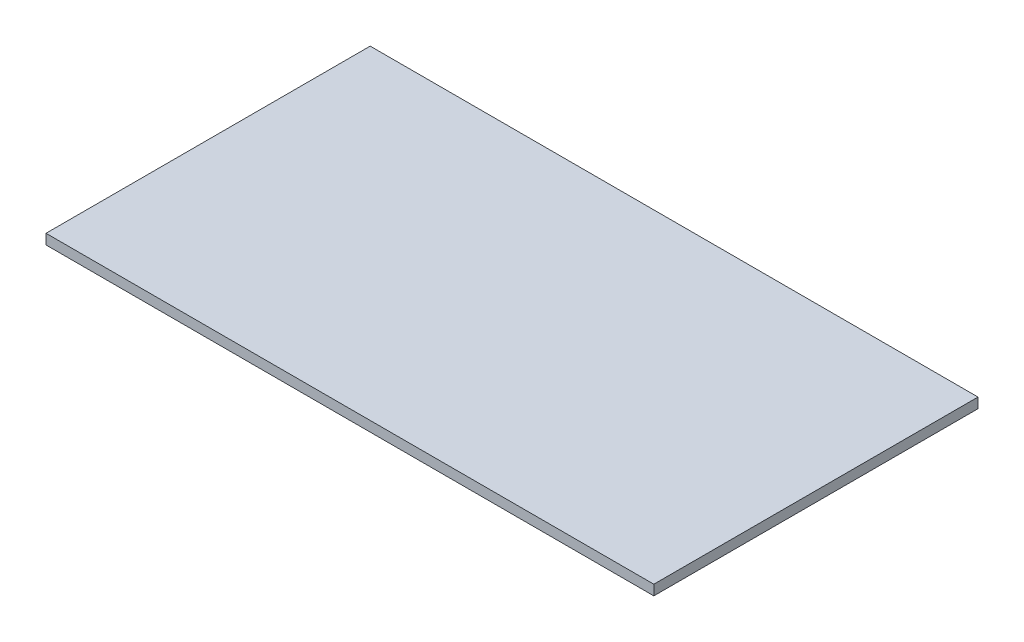
SolidWorks part; units mm, degrees
material "Cedar"
ref_plane "Front Plane" through (0, 0, 0) normal (0, 0, 1) x (1, 0, 0)
ref_plane "Top Plane" through (0, 0, 0) normal (0, 1, 0) x (1, 0, 0)
ref_plane "Right Plane" through (0, 0, 0) normal (1, 0, 0) x (0, 0, -1)
sketch "Sketch1" plane through (0, 0, 0) normal (0, 1, 0) x (1, 0, 0)
  line L1 (750, -400) -> (-750, -400)
  line L2 (750, -400) -> (750, 400)
  line L3 (750, 400) -> (-750, 400)
  line L4 (-750, -400) -> (-750, 400)
  line L5 (750, -400) -> (-750, 400) construction
  line L6 (750, 400) -> (-750, -400) construction
  point P0 (0, 0)
  dimension "D1" = 800
  dimension "D2" = 1500
extrude "Boss-Extrude1" add sketch "Sketch1" along normal blind 25
